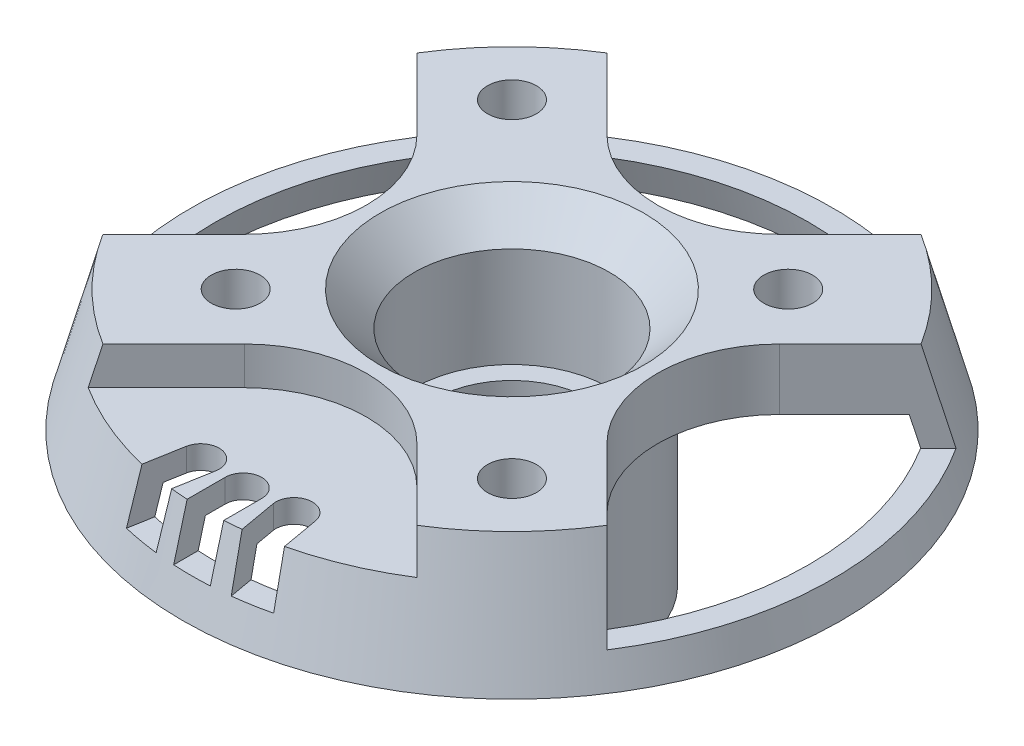
SolidWorks part; units mm, degrees
ref_plane "Front Plane" through (0, 0, 0) normal (0, 0, 1) x (1, 0, 0)
ref_plane "Top Plane" through (0, 0, 0) normal (0, 1, 0) x (1, 0, 0)
ref_plane "Right Plane" through (0, 0, 0) normal (1, 0, 0) x (0, 0, -1)
sketch "Sketch1" plane through (0, 0, 0) normal (0, 1, 0) x (1, 0, 0)
  circle A0 centre (0, 0) radius 13.5
  dimension "D1" = 27
extrude "Base size" add sketch "Sketch1" along normal blind 5
sketch "Sketch2" plane through (0, 5, 0) normal (0, 1, 0) x (1, 0, 0)
  line L0 (-9.5459, -9.5459) -> (9.5459, 9.5459) construction
  line L1 (-13.5, 0) -> (13.5, 0) construction
  line L2 (-9.5459, 9.5459) -> (9.5459, -9.5459) construction
  line L3 (0, 13.5) -> (0, -13.5) construction
  circle A0 centre (0, 0) radius 13.5 construction
  circle A1 centre (5.6569, 5.6569) radius 1
  circle A2 centre (-5.6569, -5.6569) radius 1
  circle A3 centre (-6.7175, 6.7175) radius 1
  circle A4 centre (6.7175, -6.7175) radius 1
  dimension "D2" = 2
  dimension "D1" = 45
  dimension "D3" = 16
  dimension "D4" = 19
extrude "Mounting holes" cut sketch "Sketch2" against normal up to next
sketch "Sketch3" plane through (0, 0, 0) normal (0, -1, 0) x (1, 0, 0)
  circle A0 centre (0, 0) radius 12.5
  circle A1 centre (0, 0) radius 13.5 construction
  dimension "D1" = 1
extrude "Rotor pocket" cut sketch "Sketch3" against normal blind 2.5 draft 15
chamfer "Outside chamfer" distance 5 angle 15 1 edges at (0, 5, 13.5) first distance on face at (0, 5, 13.5)
sketch "Sketch4" plane through (0, 5, 0) normal (0, 1, 0) x (1, 0, 0)
  line L0 (-8.5986, 8.5986) -> (8.5986, -8.5986) construction
  line L2 (0, 12.1603) -> (0, -12.1603) construction
  line L3 (-12.1603, 0) -> (12.1603, 0) construction
  line L4 (-8.5986, -8.5986) -> (8.5986, 8.5986) construction
  line L5 (-10.5431, 6.6541) -> (6.6541, -10.5431)
  line L6 (-6.6541, -10.5431) -> (10.5431, 6.6541)
  line L7 (-6.6541, 10.5431) -> (10.5431, -6.6541)
  line L8 (-10.5431, -6.6541) -> (6.6541, 10.5431)
  line L9 (-10.5431, 6.6541) -> (-11.2903, 7.4012)
  line L10 (-6.6541, 10.5431) -> (-7.4012, 11.2903)
  line L11 (6.6541, 10.5431) -> (7.4012, 11.2903)
  line L12 (10.5431, 6.6541) -> (11.2903, 7.4012)
  line L13 (10.5431, -6.6541) -> (11.2903, -7.4012)
  line L14 (6.6541, -10.5431) -> (7.4012, -11.2903)
  line L15 (-6.6541, -10.5431) -> (-7.4012, -11.2903)
  line L16 (-10.5431, -6.6541) -> (-11.2903, -7.4012)
  circle A0 centre (0, 0) radius 12.1603 construction
  circle A1 centre (0, 0) radius 13.5
  circle A2 centre (0, 0) radius 13.5 construction
  circle M9 centre (0, 0) radius 12.1603
  dimension "D1" = 2.75
  dimension "D2" = 2.75
extrude "Bottom pockets top" cut sketch "Sketch4" against normal blind 1.55 contours L8 L5 M9 | L9 A1 L16 L8 L5 M9 | L7 L8 M9 | L11 A1 L10 L7 L8 M9 | L6 L7 M9 | L13 A1 L12 L6 L7 M9 | L15 A1 L14 L5 L6 M9 | L6 L5 M9 region at (-12.1626, 5, 0) region at (-8.9824, 5, 0) region at (0, 5, -8.9824) region at (0, 5, -12.1626) region at (0, 5, 8.9824) region at (0, 5, 12.1626) region at (8.9824, 5, 0) region at (12.1626, 5, 0)
sketch "Sketch5" plane through (0, 3.45, 0) normal (0, 1, 0) x (1, 0, 0)
  line L0 (-11.2903, 7.4012) -> (7.4012, -11.2903)
  line L1 (-10.3204, 6.4313) -> (-3.8891, 0) construction
  line L2 (7.4012, 11.2903) -> (-11.2903, -7.4012)
  line L3 (-10.3204, -6.4313) -> (-3.8891, 0) construction
  line L4 (-7.4012, 11.2903) -> (11.2903, -7.4012)
  line L5 (-6.4313, 10.3204) -> (0, 3.8891) construction
  line L6 (-7.4012, -11.2903) -> (11.2903, 7.4012)
  line L7 (3.8891, 0) -> (10.6216, 6.7325) construction
  circle A0 centre (0, 0) radius 13.5
  circle A1 centre (0, 0) radius 13.5 construction
  line M5 (-10.6216, -6.7325) -> (-3.8891, 0)
  line M6 (-3.8891, 0) -> (-10.6216, 6.7325)
  arc M7 (-10.6216, 6.7325) -> (-10.6216, -6.7325) centre (0, 0) ccw
extrude "Bottom pockets bottom" cut sketch "Sketch5" against normal offset from surface (2.15 mm away) 1.3 contours M7 M5 M6 | L0 A0 L2 M7 | L2 A0 L4 | L4 A0 L6 region at (-11.0626, 3.45, -6.9602) region at (-9.2333, 3.45, 0) region at (0, 3.45, -9.7912) region at (9.7912, 3.45, 0) up to face at (0, 0, -12.5)
fillet "Bottom pockets fillet" radius 5 4 edges at (0, 4.225, 3.8891) (3.8891, 3.75, 0) (0, 3.75, -3.8891) (-3.8891, 3.75, 0)
sketch "Sketch6" plane through (0, 5, 0) normal (0, 1, 0) x (1, 0, 0)
  circle A0 centre (0, 0) radius 4
  dimension "D1" = 8
extrude "Cut-Extrude5" cut sketch "Sketch6" against normal up to next
chamfer "Chamfer2" distance 1.4 angle 45 1 edges at (0, 5, 4)
sketch "Sketch7" plane through (0, 2.5, 0) normal (0, -1, 0) x (1, 0, 0)
  circle A0 centre (0, 0) radius 4
  circle A1 centre (0, 0) radius 4.8
  circle A2 centre (0, 0) radius 4 construction
  dimension "D1" = 0.8
extrude "Bearing bottom" add sketch "Sketch7" along normal blind 3
sketch "Sketch8" plane through (0, -0.5, 0) normal (0, -1, 0) x (1, 0, 0)
  circle A0 centre (0, 0) radius 4.8 construction
  circle A1 centre (0, 0) radius 4.8
  circle A2 centre (0, 0) radius 3.2
  circle A3 centre (0, 0) radius 4 construction
  dimension "D1" = 0.8
extrude "Bearing separator" add sketch "Sketch8" along normal blind 1
sketch "Sketch9" plane through (0, -1.5, 0) normal (0, -1, 0) x (1, 0, 0)
  circle A0 centre (0, 0) radius 4.8 construction
  circle A1 centre (0, 0) radius 4.8
  circle A2 centre (0, 0) radius 4 construction
  circle A3 centre (0, 0) radius 4
extrude "Bearing top" add sketch "Sketch9" along normal blind 4
sketch "Sketch10" plane through (0, 3.45, 0) normal (0, 1, 0) x (1, 0, 0)
  line L0 (0, -13.5) -> (0, 13.5) construction
  line L1 (0, 0) -> (0, -11) construction
  line L2 (0, 0) -> (-1.9101, -10.8329) construction
  line L3 (-2.6439, -10.6775) -> (-3.0788, -13.1442)
  line L4 (-1.1675, -10.9379) -> (-1.6025, -13.4046)
  line L5 (-0.75, -11) -> (-0.75, -13.4792)
  line L6 (2.6439, -10.6775) -> (3.0788, -13.1442)
  line L7 (1.1675, -10.9379) -> (1.6025, -13.4046)
  line L8 (0.75, -11) -> (0.75, -13.4792)
  circle A0 centre (0, 0) radius 11
  circle A1 centre (0, 0) radius 13.5 construction
  circle A2 centre (0, -11) radius 0.75
  circle A3 centre (-1.9101, -10.8329) radius 0.75
  circle A4 centre (1.9101, -10.8329) radius 0.75
  circle A5 centre (0, 0) radius 13.5
  arc M11 (-6.7325, -10.6216) -> (6.7325, -10.6216) centre (0, 0) ccw
  dimension "D1" = 2.5
  dimension "D2" = 1.5
  dimension "D4" = 10
  dimension "D3" = 2
extrude "Cut-Extrude6" cut sketch "Sketch10" against normal offset from surface (2.05 mm away) 1.4 contours A0 A3 | L3 A3 L4 A0 | A3 L3 L4 M11 | L3 A5 L4 M11 | L5 A5 L8 M11 | A2 L5 L8 M11 | A2 A0 | A0 A2 | A4 A0 | A4 L6 A0 L7 | L6 A4 L7 M11 | L7 A5 L6 M11 region at (-1.9646, 3.45, 11.1418) region at (-1.8541, 3.45, 10.5149) region at (-2.095, 3.45, 11.8813) region at (-2.2627, 3.45, 12.8326) region at (1.9646, 3.45, 11.1418) region at (1.8541, 3.45, 10.5149) region at (0, 3.45, 10.6771) region at (0, 3.45, 11.3137) region at (2.095, 3.45, 11.8813) region at (0, 3.45, 12.0643) region at (0, 3.45, 13.0306) region at (2.2627, 3.45, 12.8326) up to face at (0, 0, -12.5)
sketch "Sketch11" plane through (0, 5, 0) normal (0, 1, 0) x (1, 0, 0)
  line L0 (6.7175, -6.7175) -> (-6.7175, 6.7175) construction
  line L1 (5.6569, 5.6569) -> (-5.6569, -5.6569) construction
  circle A0 centre (-6.7175, 6.7175) radius 1 construction
  circle A1 centre (6.7175, -6.7175) radius 1 construction
ref_axis "Center axis" through (0, 26.8978, 0) along (0, -1, 0)
